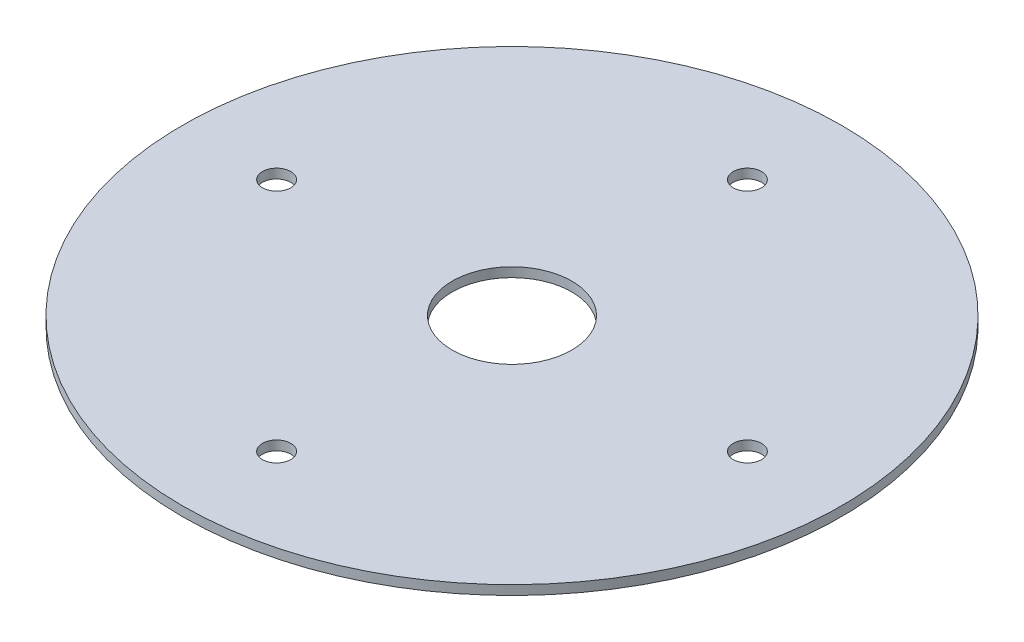
SolidWorks part; units mm, degrees
ref_plane "Front Plane" through (0, 0, 0) normal (0, 0, 1) x (1, 0, 0)
ref_plane "Top Plane" through (0, 0, 0) normal (0, 1, 0) x (1, 0, 0)
ref_plane "Right Plane" through (0, 0, 0) normal (1, 0, 0) x (0, 0, -1)
sketch "Sketch1" plane through (0, 0, 0) normal (0, 1, 0) x (1, 0, 0)
  circle A0 centre (0, 0) radius 35
extrude "Boss-Extrude1" add sketch "Sketch1" along normal blind 1
sketch "Sketch2" plane through (0, 1, 0) normal (0, 1, 0) x (1, 0, 0)
  circle A0 centre (0, 0) radius 6.35
extrude "Cut-Extrude1" cut sketch "Sketch2" against normal blind 1
sketch "Sketch3" plane through (0, 1, 0) normal (0, 1, 0) x (1, 0, 0)
  line L0 (0, 0) -> (0, 25)
  circle A0 centre (0, 25) radius 1.5
ref_axis "Axis1" through (0, 1.05, 0) along (0, -1, 0)
extrude "Cut-Extrude4" cut sketch "Sketch3" against normal blind 1 contours A0
pattern_circular "CirPattern1" count 4 over 360 about axis through (0, 1.05, 0) along (0, -1, 0) of "Cut-Extrude4"
